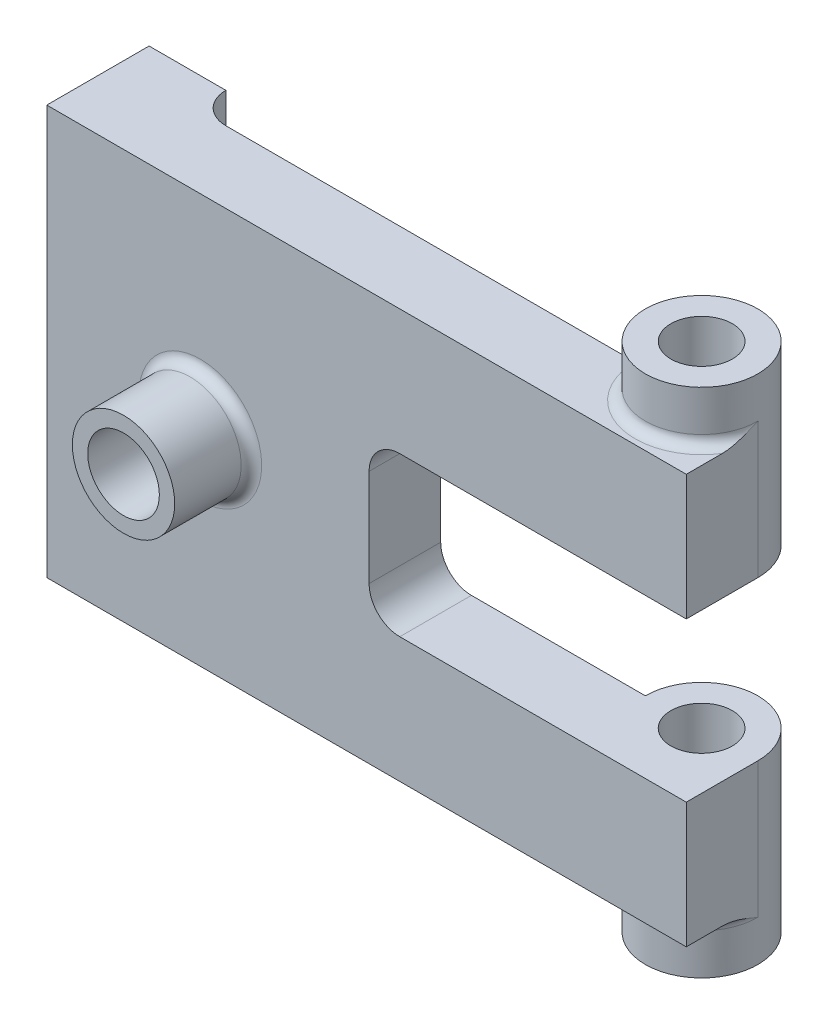
SolidWorks part; units mm, degrees
ref_plane "Front Plane" through (0, 0, 0) normal (1, 0, 0) x (0, 1, 0)
ref_plane "Top Plane" through (0, 0, 0) normal (0, 0, 1) x (0, 1, 0)
ref_plane "Right Plane" through (0, 0, 0) normal (0, 1, 0) x (-1, 0, 0)
sketch "Sketch1" plane through (0, 0, 0) normal (0, 1, 0) x (-1, 0, 0)
  line L0 (0, 0) -> (125, 0)
  line L1 (125, 0) -> (125, -20)
  line L2 (125, -20) -> (110, -20)
  line L3 (104, -14) -> (22, -14)
  line L4 (0, -14) -> (0, 0)
  arc A0 (110, -20) -> (104, -14) centre (104, -20) ccw
  arc A1 (22, -14) -> (0, -14) centre (11, -14) cw
  circle A2 centre (11, -14) radius 6
  dimension "D3" = 12
  dimension "D4" = 11
  dimension "D6" = 6
  dimension "D1" = 125
  dimension "D2" = 20
  dimension "D5" = 6
  dimension "D7" = 110
extrude "Boss-Extrude1" add sketch "Sketch1" along normal mid plane 80
sketch "Sketch3" plane through (0, 0, 0) normal (0, 1, 0) x (-1, 0, 0)
  circle A0 centre (11, -14) radius 11
  arc A1 (0, -14) -> (22, -14) centre (11, -14) ccw construction
  circle A2 centre (11, -14) radius 6 construction
  circle A3 centre (11, -14) radius 6
extrude "Boss-Extrude2" add sketch "Sketch3" along normal mid plane 100
sketch "Sketch2" plane through (0, 0, 0) normal (0, 0, 1) x (0, 1, 0)
  line L0 (40, 0) -> (-40, 0) construction
  line L1 (-15.5, 0) -> (15.5, 0)
  line L2 (-15.5, 0) -> (-15.5, 56)
  line L3 (-9.5, 62) -> (9.5, 62)
  line L4 (15.5, 0) -> (15.5, 56)
  line L5 (40, 125) -> (-40, 125) construction
  arc A0 (9.5, 62) -> (15.5, 56) centre (9.5, 56) cw
  arc A1 (-15.5, 56) -> (-9.5, 62) centre (-9.5, 56) cw
  circle A2 centre (0, 95) radius 7
  point P6 (0, 62)
  point P10 (15.5, 62)
  point P13 (-15.5, 62)
  dimension "D3" = 6
  dimension "D4" = 14
  dimension "D1" = 31
  dimension "D2" = 62
  dimension "D5" = 30
extrude "Cut-Extrude1" cut sketch "Sketch2" against normal through all both and the other way through all
sketch "Sketch4" plane through (0, 0, 0) normal (0, 0, 1) x (1, 0, 0)
  circle A0 centre (-95, 0) radius 7 construction
  circle A1 centre (-95, 0) radius 7
extrude "Extrude-Thin1" add sketch "Sketch4" along normal blind 15 thin thin type one direction wall 3
fillet "Fillet1" radius 2 3 edges at (-11, -40, -3) (-11, 40, -3) (-85, 0, 0)
